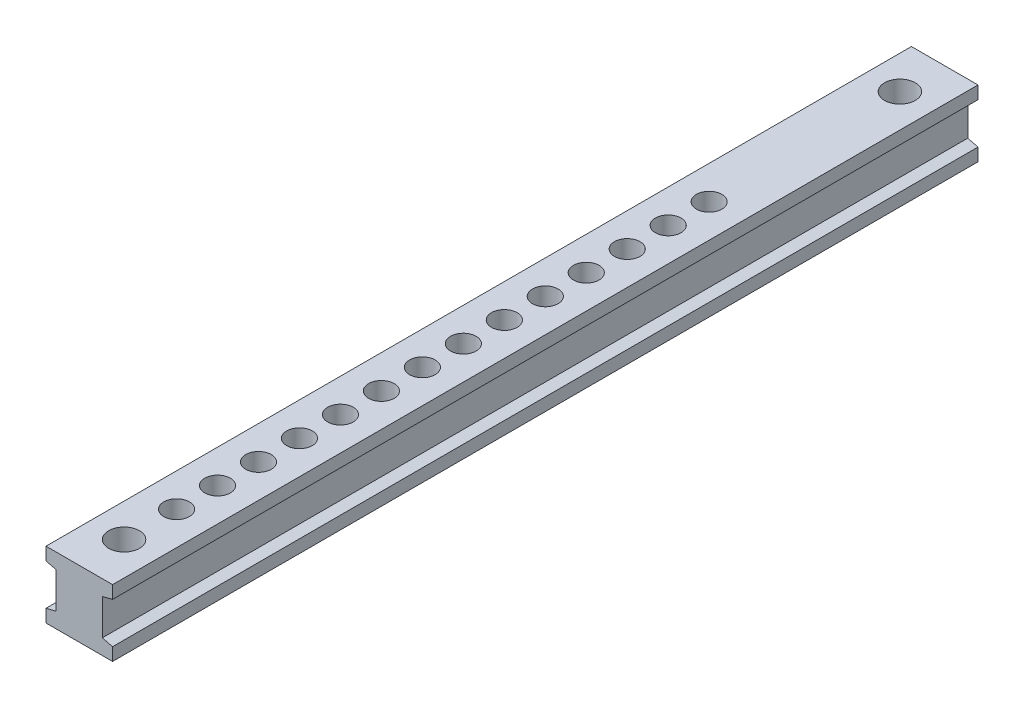
SolidWorks part; units mm, degrees
ref_plane "Front Plane" through (0, 0, 0) normal (0, 0, 1) x (1, 0, 0)
ref_plane "Top Plane" through (0, 0, 0) normal (0, 1, 0) x (1, 0, 0)
ref_plane "Right Plane" through (0, 0, 0) normal (1, 0, 0) x (0, 0, -1)
sketch "Sketch1" plane through (0, 0, 0) normal (0, 0, 1) x (1, 0, 0)
  line L0 (6.5, 4) -> (4.5, 3.5)
  line L1 (-6.5, 6.5) -> (6.5, 6.5)
  line L2 (-6.5, 6.5) -> (-6.5, -6.5)
  line L3 (-6.5, -6.5) -> (6.5, -6.5)
  line L4 (6.5, 6.5) -> (6.5, -6.5)
  line L5 (-6.5, 6.5) -> (6.5, -6.5) construction
  line L6 (-6.5, -6.5) -> (6.5, 6.5) construction
  line L7 (4.5, 3.5) -> (4.5, -3.5)
  line L8 (4.5, -3.5) -> (6.5, -4)
  line L9 (-4.5, 0) -> (4.5, 0) construction
  line L10 (0, -6.5) -> (0, 6.5) construction
  line L11 (6.5, -6.5) -> (-6.5, 6.5) construction
  line L12 (6.5, 6.5) -> (-6.5, -6.5) construction
  line L13 (-4.5, -3.5) -> (-6.5, -4)
  line L14 (-4.5, 3.5) -> (-4.5, -3.5)
  line L15 (-6.5, 6.5) -> (-6.5, -6.5)
  line L16 (-6.5, 4) -> (-4.5, 3.5)
  point P0 (0, 0)
  point P13 (0, 0)
  dimension "D1" = 13
  dimension "D2" = 13
  dimension "D3" = 7
  dimension "D4" = 2
  dimension "D5" = 8
extrude "Boss-Extrude1" add sketch "Sketch1" along normal mid plane 169 contours L2 L16 L14 L13 L3 L4 L8 L7 L0 L1 region at (0, 0, 0)
sketch "Sketch2" plane through (0, 0, 0) normal (0, 1, 0) x (1, 0, 0)
  line L0 (0, 84.5) -> (0, -84.5) construction
  line L1 (-6.5, 84.5) -> (6.5, 84.5) construction
  line L2 (-6.5, -84.5) -> (6.5, -84.5) construction
  line L3 (0, -65.5) -> (0, -57.5) construction
  circle A0 centre (0, 75.75) radius 3
  circle A1 centre (0, -75.75) radius 3
  circle A2 centre (0, -65.5) radius 2.5
  circle A3 centre (0, -57.5) radius 2.5
  circle A4 centre (0, -49.5) radius 2.5
  circle A5 centre (0, -41.5) radius 2.5
  circle A6 centre (0, -33.5) radius 2.5
  circle A7 centre (0, -25.5) radius 2.5
  circle A8 centre (0, -17.5) radius 2.5
  circle A9 centre (0, -9.5) radius 2.5
  circle A10 centre (0, -1.5) radius 2.5
  circle A11 centre (0, 6.5) radius 2.5
  circle A12 centre (0, 14.5) radius 2.5
  circle A13 centre (0, 22.5) radius 2.5
  circle A14 centre (0, 30.5) radius 2.5
  circle A15 centre (0, 38.5) radius 2.5
  dimension "D2" = 6
  dimension "D4" = 5
  dimension "D1" = 8.75
  dimension "D3" = 8.75
  dimension "D5" = 19
  dimension "D7" = 8
  dimension "D6" = 14
extrude "Cut-Extrude1" cut sketch "Sketch2" against normal through all both and the other way through all
equation "\"D3@Sketch2\"=\"D1@Sketch2\""
